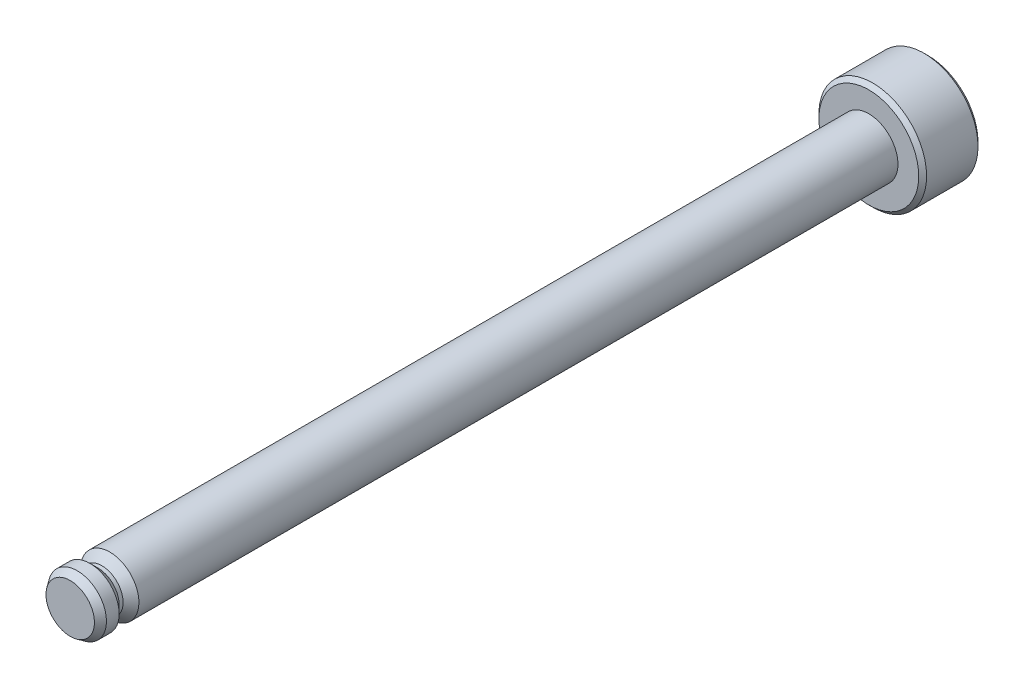
SolidWorks part; units mm, degrees
ref_plane "Front" through (0, 0, 0) normal (0, 0, 1) x (1, 0, 0)
ref_plane "Top" through (0, 0, 0) normal (0, 1, 0) x (1, 0, 0)
ref_plane "Right" through (0, 0, 0) normal (1, 0, 0) x (0, 0, -1)
sketch "Sketch2" plane through (0, 0, 0) normal (0, 0, 1) x (1, 0, 0)
  circle A0 centre (0, 0) radius 1.475
  dimension "D1" = 2.95
extrude "Shaft" add sketch "Sketch2" along normal blind 40.4
sketch "Sketch5" plane through (0, 0, 0) normal (0, 0, 1) x (1, 0, 0)
  circle A0 centre (0, 0) radius 2.725
  dimension "D1" = 5.45
extrude "Head" add sketch "Sketch5" against normal blind 3
chamfer "Chamfer1" distance 0.25 angle 55 1 edges at (1.475, 0, 40.4) first distance on face at (1.475, 0, 40.4)
chamfer "Deburs" distance 0.2 angle 45 2 edges at (2.725, 0, 0) (2.725, 0, -3)
sketch "Sketch6" plane through (0, 0, 0) normal (1, 0, 0) x (0, 0, -1)
  line L0 (0, 0) -> (-38.9, 0) construction
  line L1 (-38.9, 0) -> (-38.9, 1.075) construction
  line L2 (0, 1.475) -> (-40.043, 1.475) construction
  line L3 (-39.4, 1.475) -> (-38.4, 1.475)
  line L4 (-38.4, 1.475) -> (-38.8, 1.075)
  line L5 (-38.8, 1.075) -> (-39, 1.075)
  line L6 (-39, 1.075) -> (-39.4, 1.475)
  line L7 (-38.9, 1.075) -> (-38.9, 1.475) construction
  dimension "D1" = 38.9
  dimension "D2" = 0.4
  dimension "D3" = 1
revolve "e-Clip Notch Long" cut sketch "Sketch6" angle 360 about L0
equation "\"D1@Sketch2\"=\"Plastic Hardware OD@Box Assy.Assembly\""
equation "\"D1@Sketch5\"=\"Hardware Head Countersink Diameter@Box Assy.Assembly\"-.3mm"
equation "\"D1@Head\"=\"Countersink Depth@Box Assy.Assembly\""
equation "\"Length\"= 40mm"
equation "\"D1@Shaft\"=\"Length\"+.4mm"
equation "\"D1@Sketch6\"=\"Length\"-1.1mm"
